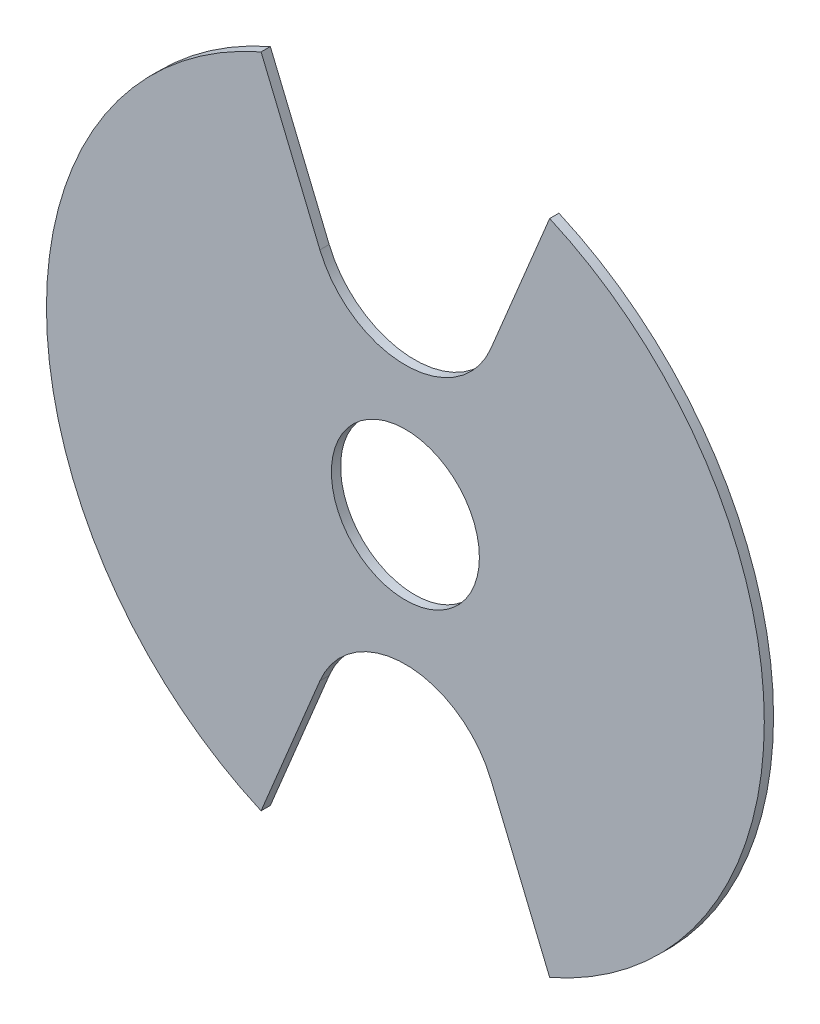
SolidWorks part; units mm, degrees
ref_plane "Front Plane" through (0, 0, 0) normal (0, 0, 1) x (1, 0, 0)
ref_plane "Top Plane" through (0, 0, 0) normal (0, 1, 0) x (1, 0, 0)
ref_plane "Right Plane" through (0, 0, 0) normal (1, 0, 0) x (0, 0, -1)
sketch "Esquisse1" plane through (0, 0, 0) normal (0, 0, 1) x (1, 0, 0)
  circle A0 centre (0, 0) radius 97
  circle A1 centre (0, 0) radius 20
  dimension "D1" = 194
  dimension "D2" = 40
extrude "Main" add sketch "Esquisse1" along normal blind 2.5
sketch "Esquisse2" plane through (0, 0, 2.5) normal (0, 0, 1) x (1, 0, 0)
  line L0 (-23.097, 50.4329) -> (-38.9959, 88.8162)
  line L1 (23.097, 50.4329) -> (38.9959, 88.8162)
  arc A0 (-23.097, 50.4329) -> (23.097, 50.4329) centre (0, 60) ccw
  circle A1 centre (0, 0) radius 97 construction
  dimension "D2" = 25
  dimension "D1" = 45
  dimension "D3" = 60
extrude "Enlèv. mat.-Extru.1" cut sketch "Esquisse2" against normal through all and the other way through all
mirror "Symétrie1" about plane through (0, 0, 0) normal (0, 1, 0) of "Enlèv. mat.-Extru.1"
